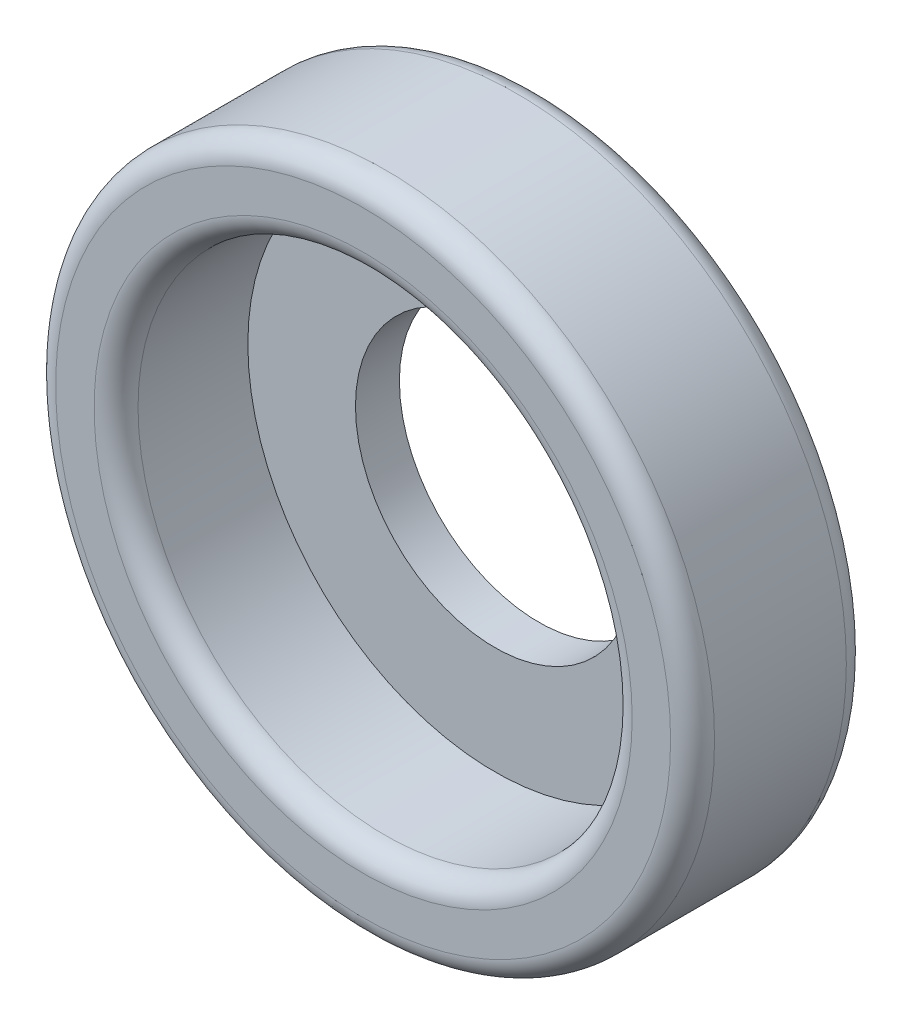
SolidWorks part; units mm, degrees
ref_plane "Front Plane" through (0, 0, 0) normal (0, 0, 1) x (1, 0, 0)
ref_plane "Top Plane" through (0, 0, 0) normal (0, 1, 0) x (1, 0, 0)
ref_plane "Right Plane" through (0, 0, 0) normal (1, 0, 0) x (0, 0, -1)
sketch "Sketch1" plane through (0, 0, 0) normal (0, 0, 1) x (1, 0, 0)
  circle A0 centre (0, 0) radius 11.25
  circle A1 centre (0, 0) radius 15
  circle A2 centre (0, 0) radius 6.35
  dimension "D1" = 22.5
  dimension "D2" = 30
  dimension "D3" = 12.7
extrude "Boss-Extrude1" add sketch "Sketch1" along normal blind 8 contours A1 A0 region at (-14.5757, 0, 0)
extrude "Boss-Extrude2" add sketch "Sketch1<3>" along normal blind 2 contours A0 A2 region at (-10.9318, 0, 0)
sketch "Sketch1<3>" plane through (0, 0, 0) normal (0, 0, 1) x (1, 0, 0) same geometry as "Sketch1"
fillet "Fillet1" radius 1 3 edges at (11.25, 0, 8) (15, 0, 8) (15, 0, 0)
